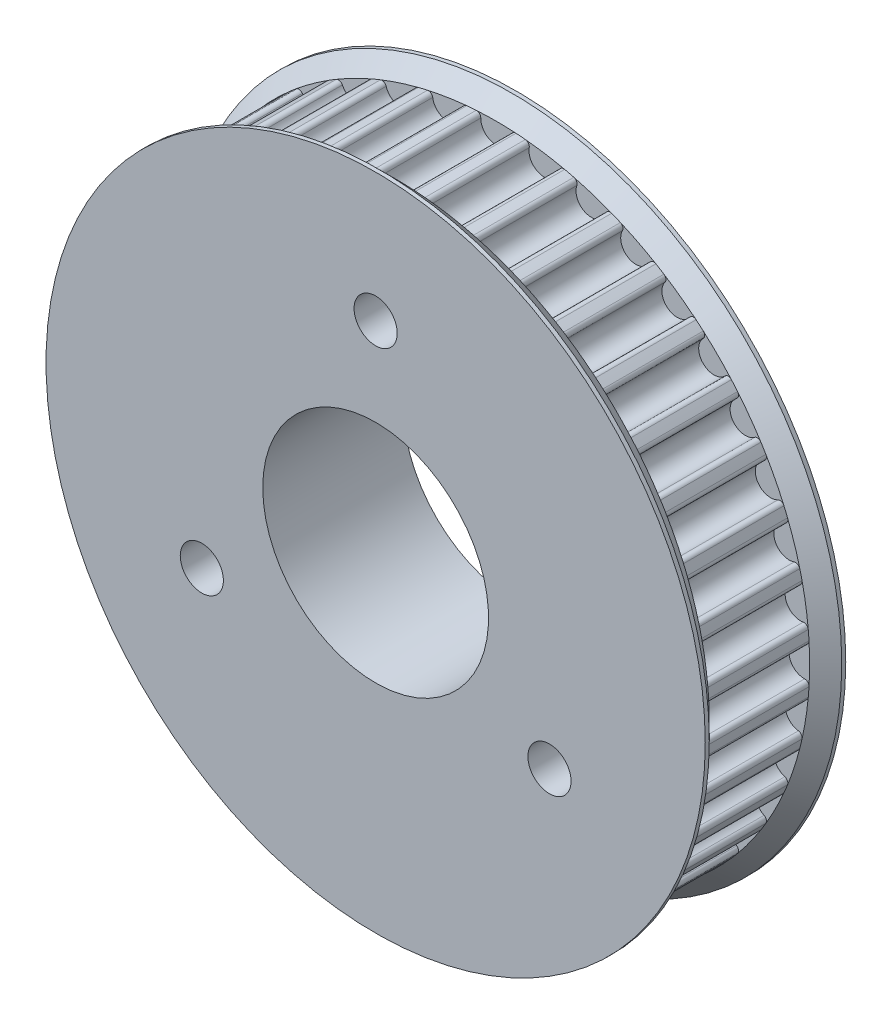
SolidWorks part; units mm, degrees
other "Markup1"
sketch "Sketch10" plane through (-16.9255, -16.9255, 12) normal (-0.253, -0.2476, 0.9352) x (0.4078, 0.8493, 0.3352)
ref_plane "Front Plane" through (0, 0, 0) normal (0, 0, 1) x (1, 0, 0)
ref_plane "Top Plane" through (0, 0, 0) normal (0, 1, 0) x (1, 0, 0)
ref_plane "Right Plane" through (0, 0, 0) normal (1, 0, 0) x (0, 0, -1)
sketch "Sketch1" plane through (0, 0, 0) normal (0, 0, 1) x (1, 0, 0)
  line L0 (0, 31.831) -> (0, 0) construction
  line L1 (0, 0) -> (4.9795, 31.4391) construction
  line L2 (0, 30.706) -> (1.9545, 30.7489) construction
  line L3 (2.8797, 30.6761) -> (4.8035, 30.3279) construction
  line L4 (1.9545, 30.7489) -> (1.9818, 31.1781) construction
  line L5 (2.8797, 30.6761) -> (2.9199, 31.1042) construction
  arc A0 (0, 31.831) -> (4.9795, 31.4391) centre (0, 0) cw construction
  circle A1 centre (0, 0) radius 31.831 construction
  circle A2 centre (0, 0) radius 31.241
  circle A3 centre (0, 0) radius 29.181
  circle A8 centre (0, 0) radius 32.981 construction
  circle A9 centre (0, 30.706) radius 1.525
  circle A10 centre (4.8035, 30.3279) radius 1.525
  circle A11 centre (1.9545, 30.7489) radius 0.43
  circle A12 centre (2.8797, 30.6761) radius 0.43
  point P18 (0, 29.181)
  point P19 (4.2572, 15.8881)
  point P20 (4.2572, 15.8881)
  point P21 (1.5246, 30.7395)
  point P23 (3.3029, 30.5995)
  dimension "D6" = 3.05
  dimension "D7" = 3.05
  dimension "D8" = 0.86
  dimension "D9" = 0.86
  dimension "D5" = 3.8
  dimension "D1" = 9
  dimension "D2" = 5
  dimension "D3" = 0.59
  dimension "D4" = 2.06
extrude "Boss-Extrude1" add sketch "Sketch1" along normal blind 10 contours A2
extrude "Cut-Extrude1" cut sketch "Sketch1<5>" along normal through all contours A11 A2 A9 | A12 A10 A2 | A9 | A10 region at (3.2858, 30.9603, 0) region at (1.5979, 31.0932, 0)
sketch "Sketch1<5>" plane through (0, 0, 0) normal (0, 0, 1) x (1, 0, 0) same geometry as "Sketch1"
pattern_circular "CirPattern3" count 40 over 360 about axis through (0, 0, 10) along (0, 0, 1) of "Cut-Extrude1"
sketch "Sketch2" plane through (0, 0, 10) normal (0, 0, 1) x (1, 0, 0)
  circle A0 centre (0, 0) radius 32.981 construction
  arc A81 (-30.7395, -1.5246) -> (-30.7395, 1.5246) centre (-30.706, 0) ccw
  arc A82 (-30.7395, -1.5246) -> (-30.7395, 1.5246) centre (-30.706, 0) ccw
  arc A83 (-30.7395, -1.5246) -> (-31.1781, -1.9818) centre (-30.7489, -1.9545) ccw
  arc A84 (-30.7395, -1.5246) -> (-31.1781, -1.9818) centre (-30.7489, -1.9545) ccw
  arc A85 (-31.1781, -1.9818) -> (-31.1042, -2.9199) centre (0, 0) ccw
  arc A86 (-31.1781, -1.9818) -> (-31.1042, -2.9199) centre (0, 0) ccw
  arc A87 (-31.1042, -2.9199) -> (-30.5995, -3.3029) centre (-30.6761, -2.8797) ccw
  arc A88 (-31.1042, -2.9199) -> (-30.5995, -3.3029) centre (-30.6761, -2.8797) ccw
  arc A89 (-30.1225, -6.3146) -> (-30.5995, -3.3029) centre (-30.3279, -4.8035) ccw
  arc A90 (-30.1225, -6.3146) -> (-30.5995, -3.3029) centre (-30.3279, -4.8035) ccw
  arc A91 (-30.1225, -6.3146) -> (-30.4842, -6.8347) centre (-30.0646, -6.7407) ccw
  arc A92 (-30.1225, -6.3146) -> (-30.4842, -6.8347) centre (-30.0646, -6.7407) ccw
  arc A93 (-30.4842, -6.8347) -> (-30.2645, -7.7497) centre (0, 0) ccw
  arc A95 (-30.4842, -6.8347) -> (-30.2645, -7.7497) centre (0, 0) ccw
  arc A97 (-30.2645, -7.7497) -> (-29.7061, -8.049) centre (-29.848, -7.6431) ccw
  arc A99 (-30.2645, -7.7497) -> (-29.7061, -8.049) centre (-29.848, -7.6431) ccw
  arc A101 (-28.7639, -10.949) -> (-29.7061, -8.049) centre (-29.2031, -9.4887) ccw
  arc A103 (-28.7639, -10.949) -> (-29.7061, -8.049) centre (-29.2031, -9.4887) ccw
  arc A105 (-28.7639, -10.949) -> (-29.0397, -11.5194) centre (-28.64, -11.3608) ccw
  arc A107 (-28.7639, -10.949) -> (-29.0397, -11.5194) centre (-28.64, -11.3608) ccw
  arc A109 (-29.0397, -11.5194) -> (-28.6796, -12.3887) centre (0, 0) ccw
  arc A111 (-29.0397, -11.5194) -> (-28.6796, -12.3887) centre (0, 0) ccw
  arc A112 (-28.6796, -12.3887) -> (-28.0813, -12.597) centre (-28.2848, -12.2182) ccw
  arc A114 (-28.6796, -12.3887) -> (-28.0813, -12.597) centre (-28.2848, -12.2182) ccw
  arc A116 (-26.6969, -15.3139) -> (-28.0813, -12.597) centre (-27.3592, -13.9402) ccw
  arc A118 (-26.6969, -15.3139) -> (-28.0813, -12.597) centre (-27.3592, -13.9402) ccw
  arc A122 (-26.6969, -15.3139) -> (-26.8801, -15.9203) centre (-26.5102, -15.7012) ccw
  arc A126 (-26.6969, -15.3139) -> (-26.8801, -15.9203) centre (-26.5102, -15.7012) ccw
  arc A130 (-26.8801, -15.9203) -> (-26.3885, -16.7227) centre (0, 0) ccw
  arc A134 (-26.8801, -15.9203) -> (-26.3885, -16.7227) centre (0, 0) ccw
  arc A138 (-26.3885, -16.7227) -> (-25.7649, -16.8348) centre (-26.0253, -16.4925) ccw
  arc A142 (-26.3885, -16.7227) -> (-25.7649, -16.8348) centre (-26.0253, -16.4925) ccw
  arc A146 (-23.9726, -19.3017) -> (-25.7649, -16.8348) centre (-24.8417, -18.0485) ccw
  arc A150 (-23.9726, -19.3017) -> (-25.7649, -16.8348) centre (-24.8417, -18.0485) ccw
  arc A154 (-23.9726, -19.3017) -> (-24.0587, -19.9293) centre (-23.7276, -19.655) ccw
  arc A158 (-23.9726, -19.3017) -> (-24.0587, -19.9293) centre (-23.7276, -19.655) ccw
  arc A162 (-24.0587, -19.9293) -> (-23.4476, -20.6449) centre (0, 0) ccw
  arc A166 (-24.0587, -19.9293) -> (-23.4476, -20.6449) centre (0, 0) ccw
  arc A170 (-23.4476, -20.6449) -> (-22.8142, -20.658) centre (-23.1248, -20.3607) ccw
  arc A174 (-23.4476, -20.6449) -> (-22.8142, -20.658) centre (-23.1248, -20.3607) ccw
  arc A178 (-20.658, -22.8142) -> (-22.8142, -20.658) centre (-21.7124, -21.7124) ccw
  arc A182 (-20.658, -22.8142) -> (-22.8142, -20.658) centre (-21.7124, -21.7124) ccw
  arc A186 (-20.658, -22.8142) -> (-20.6449, -23.4476) centre (-20.3607, -23.1248) ccw
  arc A190 (-20.658, -22.8142) -> (-20.6449, -23.4476) centre (-20.3607, -23.1248) ccw
  arc A193 (-20.6449, -23.4476) -> (-19.9293, -24.0587) centre (0, 0) ccw
  arc A195 (-20.6449, -23.4476) -> (-19.9293, -24.0587) centre (0, 0) ccw
  arc A197 (-19.9293, -24.0587) -> (-19.3017, -23.9726) centre (-19.655, -23.7276) ccw
  arc A199 (-19.9293, -24.0587) -> (-19.3017, -23.9726) centre (-19.655, -23.7276) ccw
  arc A201 (-16.8348, -25.7649) -> (-19.3017, -23.9726) centre (-18.0485, -24.8417) ccw
  arc A203 (-16.8348, -25.7649) -> (-19.3017, -23.9726) centre (-18.0485, -24.8417) ccw
  arc A205 (-16.8348, -25.7649) -> (-16.7227, -26.3885) centre (-16.4925, -26.0253) ccw
  arc A207 (-16.8348, -25.7649) -> (-16.7227, -26.3885) centre (-16.4925, -26.0253) ccw
  arc A209 (-16.7227, -26.3885) -> (-15.9203, -26.8801) centre (0, 0) ccw
  arc A211 (-16.7227, -26.3885) -> (-15.9203, -26.8801) centre (0, 0) ccw
  arc A213 (-15.9203, -26.8801) -> (-15.3139, -26.6969) centre (-15.7012, -26.5102) ccw
  arc A215 (-15.9203, -26.8801) -> (-15.3139, -26.6969) centre (-15.7012, -26.5102) ccw
  arc A217 (-12.597, -28.0813) -> (-15.3139, -26.6969) centre (-13.9402, -27.3592) ccw
  arc A221 (-12.597, -28.0813) -> (-15.3139, -26.6969) centre (-13.9402, -27.3592) ccw
  arc A225 (-12.597, -28.0813) -> (-12.3887, -28.6796) centre (-12.2182, -28.2848) ccw
  arc A229 (-12.597, -28.0813) -> (-12.3887, -28.6796) centre (-12.2182, -28.2848) ccw
  arc A233 (-12.3887, -28.6796) -> (-11.5194, -29.0397) centre (0, 0) ccw
  arc A241 (-12.3887, -28.6796) -> (-11.5194, -29.0397) centre (0, 0) ccw
  arc A245 (-11.5194, -29.0397) -> (-10.949, -28.7639) centre (-11.3608, -28.64) ccw
  arc A247 (-11.5194, -29.0397) -> (-10.949, -28.7639) centre (-11.3608, -28.64) ccw
  arc A249 (-8.049, -29.7061) -> (-10.949, -28.7639) centre (-9.4887, -29.2031) ccw
  arc A251 (-8.049, -29.7061) -> (-10.949, -28.7639) centre (-9.4887, -29.2031) ccw
  arc A253 (-8.049, -29.7061) -> (-7.7497, -30.2645) centre (-7.6431, -29.848) ccw
  arc A255 (-8.049, -29.7061) -> (-7.7497, -30.2645) centre (-7.6431, -29.848) ccw
  arc A257 (-7.7497, -30.2645) -> (-6.8347, -30.4842) centre (0, 0) ccw
  arc A259 (-7.7497, -30.2645) -> (-6.8347, -30.4842) centre (0, 0) ccw
  arc A261 (-6.8347, -30.4842) -> (-6.3146, -30.1225) centre (-6.7407, -30.0646) ccw
  arc A263 (-6.8347, -30.4842) -> (-6.3146, -30.1225) centre (-6.7407, -30.0646) ccw
  arc A373 (3.3029, 30.5995) -> (6.3146, 30.1225) centre (4.8035, 30.3279) ccw
  arc A374 (3.3029, 30.5995) -> (2.9199, 31.1042) centre (2.8797, 30.6761) ccw
  arc A375 (2.9199, 31.1042) -> (1.9818, 31.1781) centre (0, 0) ccw
  arc A376 (1.9818, 31.1781) -> (1.5246, 30.7395) centre (1.9545, 30.7489) ccw
  arc A377 (-1.5246, 30.7395) -> (1.5246, 30.7395) centre (0, 30.706) ccw
  arc A378 (-1.5246, 30.7395) -> (-1.9818, 31.1781) centre (-1.9545, 30.7489) ccw
  arc A379 (-1.9818, 31.1781) -> (-2.9199, 31.1042) centre (0, 0) ccw
  arc A380 (-2.9199, 31.1042) -> (-3.3029, 30.5995) centre (-2.8797, 30.6761) ccw
  arc A381 (-6.3146, 30.1225) -> (-3.3029, 30.5995) centre (-4.8035, 30.3279) ccw
  arc A382 (-6.3146, 30.1225) -> (-6.8347, 30.4842) centre (-6.7407, 30.0646) ccw
  arc A383 (-6.8347, 30.4842) -> (-7.7497, 30.2645) centre (0, 0) ccw
  arc A384 (-7.7497, 30.2645) -> (-8.049, 29.7061) centre (-7.6431, 29.848) ccw
  arc A385 (-10.949, 28.7639) -> (-8.049, 29.7061) centre (-9.4887, 29.2031) ccw
  arc A386 (-10.949, 28.7639) -> (-11.5194, 29.0397) centre (-11.3608, 28.64) ccw
  arc A387 (-11.5194, 29.0397) -> (-12.3887, 28.6796) centre (0, 0) ccw
  arc A388 (-12.3887, 28.6796) -> (-12.597, 28.0813) centre (-12.2182, 28.2848) ccw
  arc A389 (-15.3139, 26.6969) -> (-12.597, 28.0813) centre (-13.9402, 27.3592) ccw
  arc A390 (-15.3139, 26.6969) -> (-15.9203, 26.8801) centre (-15.7012, 26.5102) ccw
  arc A391 (-15.9203, 26.8801) -> (-16.7227, 26.3885) centre (0, 0) ccw
  arc A392 (-16.7227, 26.3885) -> (-16.8348, 25.7649) centre (-16.4925, 26.0253) ccw
  arc A393 (-19.3017, 23.9726) -> (-16.8348, 25.7649) centre (-18.0485, 24.8417) ccw
  arc A394 (-19.3017, 23.9726) -> (-19.9293, 24.0587) centre (-19.655, 23.7276) ccw
  arc A395 (-19.9293, 24.0587) -> (-20.6449, 23.4476) centre (0, 0) ccw
  arc A396 (-20.6449, 23.4476) -> (-20.658, 22.8142) centre (-20.3607, 23.1248) ccw
  arc A397 (-22.8142, 20.658) -> (-20.658, 22.8142) centre (-21.7124, 21.7124) ccw
  arc A398 (-22.8142, 20.658) -> (-23.4476, 20.6449) centre (-23.1248, 20.3607) ccw
  arc A399 (-23.4476, 20.6449) -> (-24.0587, 19.9293) centre (0, 0) ccw
  arc A400 (-24.0587, 19.9293) -> (-23.9726, 19.3017) centre (-23.7276, 19.655) ccw
  arc A401 (-25.7649, 16.8348) -> (-23.9726, 19.3017) centre (-24.8417, 18.0485) ccw
  arc A402 (-25.7649, 16.8348) -> (-26.3885, 16.7227) centre (-26.0253, 16.4925) ccw
  arc A403 (-26.3885, 16.7227) -> (-26.8801, 15.9203) centre (0, 0) ccw
  arc A404 (-26.8801, 15.9203) -> (-26.6969, 15.3139) centre (-26.5102, 15.7012) ccw
  arc A405 (-28.0813, 12.597) -> (-26.6969, 15.3139) centre (-27.3592, 13.9402) ccw
  arc A406 (-28.0813, 12.597) -> (-28.6796, 12.3887) centre (-28.2848, 12.2182) ccw
  arc A407 (-28.6796, 12.3887) -> (-29.0397, 11.5194) centre (0, 0) ccw
  arc A408 (-29.0397, 11.5194) -> (-28.7639, 10.949) centre (-28.64, 11.3608) ccw
  arc A409 (-29.7061, 8.049) -> (-28.7639, 10.949) centre (-29.2031, 9.4887) ccw
  arc A410 (-29.7061, 8.049) -> (-30.2645, 7.7497) centre (-29.848, 7.6431) ccw
  arc A411 (-30.2645, 7.7497) -> (-30.4842, 6.8347) centre (0, 0) ccw
  arc A412 (-30.4842, 6.8347) -> (-30.1225, 6.3146) centre (-30.0646, 6.7407) ccw
  arc A413 (-30.5995, 3.3029) -> (-30.1225, 6.3146) centre (-30.3279, 4.8035) ccw
  arc A414 (-30.5995, 3.3029) -> (-31.1042, 2.9199) centre (-30.6761, 2.8797) ccw
  arc A415 (-31.1042, 2.9199) -> (-31.1781, 1.9818) centre (0, 0) ccw
  arc A416 (-31.1781, 1.9818) -> (-30.7395, 1.5246) centre (-30.7489, 1.9545) ccw
  arc A649 (3.3029, 30.5995) -> (6.3146, 30.1225) centre (4.8035, 30.3279) ccw
  arc A650 (3.3029, 30.5995) -> (2.9199, 31.1042) centre (2.8797, 30.6761) ccw
  arc A651 (2.9199, 31.1042) -> (1.9818, 31.1781) centre (0, 0) ccw
  arc A652 (1.9818, 31.1781) -> (1.5246, 30.7395) centre (1.9545, 30.7489) ccw
  arc A653 (-1.5246, 30.7395) -> (1.5246, 30.7395) centre (0, 30.706) ccw
  arc A654 (-1.5246, 30.7395) -> (-1.9818, 31.1781) centre (-1.9545, 30.7489) ccw
  arc A655 (-1.9818, 31.1781) -> (-2.9199, 31.1042) centre (0, 0) ccw
  arc A656 (-2.9199, 31.1042) -> (-3.3029, 30.5995) centre (-2.8797, 30.6761) ccw
  arc A657 (-6.3146, 30.1225) -> (-3.3029, 30.5995) centre (-4.8035, 30.3279) ccw
  arc A658 (-6.3146, 30.1225) -> (-6.8347, 30.4842) centre (-6.7407, 30.0646) ccw
  arc A659 (-6.8347, 30.4842) -> (-7.7497, 30.2645) centre (0, 0) ccw
  arc A660 (-7.7497, 30.2645) -> (-8.049, 29.7061) centre (-7.6431, 29.848) ccw
  arc A661 (-10.949, 28.7639) -> (-8.049, 29.7061) centre (-9.4887, 29.2031) ccw
  arc A662 (-10.949, 28.7639) -> (-11.5194, 29.0397) centre (-11.3608, 28.64) ccw
  arc A663 (-11.5194, 29.0397) -> (-12.3887, 28.6796) centre (0, 0) ccw
  arc A664 (-12.3887, 28.6796) -> (-12.597, 28.0813) centre (-12.2182, 28.2848) ccw
  arc A665 (-15.3139, 26.6969) -> (-12.597, 28.0813) centre (-13.9402, 27.3592) ccw
  arc A666 (-15.3139, 26.6969) -> (-15.9203, 26.8801) centre (-15.7012, 26.5102) ccw
  arc A667 (-15.9203, 26.8801) -> (-16.7227, 26.3885) centre (0, 0) ccw
  arc A668 (-16.7227, 26.3885) -> (-16.8348, 25.7649) centre (-16.4925, 26.0253) ccw
  arc A669 (-19.3017, 23.9726) -> (-16.8348, 25.7649) centre (-18.0485, 24.8417) ccw
  arc A670 (-19.3017, 23.9726) -> (-19.9293, 24.0587) centre (-19.655, 23.7276) ccw
  arc A671 (-19.9293, 24.0587) -> (-20.6449, 23.4476) centre (0, 0) ccw
  arc A672 (-20.6449, 23.4476) -> (-20.658, 22.8142) centre (-20.3607, 23.1248) ccw
  arc A673 (-22.8142, 20.658) -> (-20.658, 22.8142) centre (-21.7124, 21.7124) ccw
  arc A674 (-22.8142, 20.658) -> (-23.4476, 20.6449) centre (-23.1248, 20.3607) ccw
  arc A675 (-23.4476, 20.6449) -> (-24.0587, 19.9293) centre (0, 0) ccw
  arc A676 (-24.0587, 19.9293) -> (-23.9726, 19.3017) centre (-23.7276, 19.655) ccw
  arc A677 (-25.7649, 16.8348) -> (-23.9726, 19.3017) centre (-24.8417, 18.0485) ccw
  arc A678 (-25.7649, 16.8348) -> (-26.3885, 16.7227) centre (-26.0253, 16.4925) ccw
  arc A679 (-26.3885, 16.7227) -> (-26.8801, 15.9203) centre (0, 0) ccw
  arc A680 (-26.8801, 15.9203) -> (-26.6969, 15.3139) centre (-26.5102, 15.7012) ccw
  arc A681 (-28.0813, 12.597) -> (-26.6969, 15.3139) centre (-27.3592, 13.9402) ccw
  arc A682 (-28.0813, 12.597) -> (-28.6796, 12.3887) centre (-28.2848, 12.2182) ccw
  arc A683 (-28.6796, 12.3887) -> (-29.0397, 11.5194) centre (0, 0) ccw
  arc A684 (-29.0397, 11.5194) -> (-28.7639, 10.949) centre (-28.64, 11.3608) ccw
  arc A685 (-29.7061, 8.049) -> (-28.7639, 10.949) centre (-29.2031, 9.4887) ccw
  arc A686 (-29.7061, 8.049) -> (-30.2645, 7.7497) centre (-29.848, 7.6431) ccw
  arc A687 (-30.2645, 7.7497) -> (-30.4842, 6.8347) centre (0, 0) ccw
  arc A688 (-30.4842, 6.8347) -> (-30.1225, 6.3146) centre (-30.0646, 6.7407) ccw
  arc A689 (-30.5995, 3.3029) -> (-30.1225, 6.3146) centre (-30.3279, 4.8035) ccw
  arc A690 (-30.5995, 3.3029) -> (-31.1042, 2.9199) centre (-30.6761, 2.8797) ccw
  arc A691 (-31.1042, 2.9199) -> (-31.1781, 1.9818) centre (0, 0) ccw
  arc A692 (-31.1781, 1.9818) -> (-30.7395, 1.5246) centre (-30.7489, 1.9545) ccw
  arc A715 (-3.3029, -30.5995) -> (-6.3146, -30.1225) centre (-4.8035, -30.3279) ccw
  arc A716 (-3.3029, -30.5995) -> (-6.3146, -30.1225) centre (-4.8035, -30.3279) ccw
  arc A717 (-3.3029, -30.5995) -> (-2.9199, -31.1042) centre (-2.8797, -30.6761) ccw
  arc A718 (-3.3029, -30.5995) -> (-2.9199, -31.1042) centre (-2.8797, -30.6761) ccw
  arc A719 (-2.9199, -31.1042) -> (-1.9818, -31.1781) centre (0, 0) ccw
  arc A720 (-2.9199, -31.1042) -> (-1.9818, -31.1781) centre (0, 0) ccw
  arc A721 (-1.9818, -31.1781) -> (-1.5246, -30.7395) centre (-1.9545, -30.7489) ccw
  arc A722 (-1.9818, -31.1781) -> (-1.5246, -30.7395) centre (-1.9545, -30.7489) ccw
  arc A723 (1.5246, -30.7395) -> (-1.5246, -30.7395) centre (0, -30.706) ccw
  arc A724 (1.5246, -30.7395) -> (-1.5246, -30.7395) centre (0, -30.706) ccw
  arc A725 (1.5246, -30.7395) -> (1.9818, -31.1781) centre (1.9545, -30.7489) ccw
  arc A726 (1.5246, -30.7395) -> (1.9818, -31.1781) centre (1.9545, -30.7489) ccw
  arc A727 (1.9818, -31.1781) -> (2.9199, -31.1042) centre (0, 0) ccw
  arc A728 (1.9818, -31.1781) -> (2.9199, -31.1042) centre (0, 0) ccw
  arc A729 (2.9199, -31.1042) -> (3.3029, -30.5995) centre (2.8797, -30.6761) ccw
  arc A730 (2.9199, -31.1042) -> (3.3029, -30.5995) centre (2.8797, -30.6761) ccw
  arc A731 (6.3146, -30.1225) -> (3.3029, -30.5995) centre (4.8035, -30.3279) ccw
  arc A732 (6.3146, -30.1225) -> (3.3029, -30.5995) centre (4.8035, -30.3279) ccw
  arc A733 (6.3146, -30.1225) -> (6.8347, -30.4842) centre (6.7407, -30.0646) ccw
  arc A734 (6.3146, -30.1225) -> (6.8347, -30.4842) centre (6.7407, -30.0646) ccw
  arc A735 (6.8347, -30.4842) -> (7.7497, -30.2645) centre (0, 0) ccw
  arc A736 (6.8347, -30.4842) -> (7.7497, -30.2645) centre (0, 0) ccw
  arc A737 (7.7497, -30.2645) -> (8.049, -29.7061) centre (7.6431, -29.848) ccw
  arc A738 (7.7497, -30.2645) -> (8.049, -29.7061) centre (7.6431, -29.848) ccw
  arc A739 (10.949, -28.7639) -> (8.049, -29.7061) centre (9.4887, -29.2031) ccw
  arc A740 (10.949, -28.7639) -> (8.049, -29.7061) centre (9.4887, -29.2031) ccw
  arc A741 (10.949, -28.7639) -> (11.5194, -29.0397) centre (11.3608, -28.64) ccw
  arc A742 (10.949, -28.7639) -> (11.5194, -29.0397) centre (11.3608, -28.64) ccw
  arc A743 (11.5194, -29.0397) -> (12.3887, -28.6796) centre (0, 0) ccw
  arc A744 (11.5194, -29.0397) -> (12.3887, -28.6796) centre (0, 0) ccw
  arc A745 (12.3887, -28.6796) -> (12.597, -28.0813) centre (12.2182, -28.2848) ccw
  arc A746 (12.3887, -28.6796) -> (12.597, -28.0813) centre (12.2182, -28.2848) ccw
  arc A747 (15.3139, -26.6969) -> (12.597, -28.0813) centre (13.9402, -27.3592) ccw
  arc A748 (15.3139, -26.6969) -> (12.597, -28.0813) centre (13.9402, -27.3592) ccw
  arc A749 (15.3139, -26.6969) -> (15.9203, -26.8801) centre (15.7012, -26.5102) ccw
  arc A750 (15.3139, -26.6969) -> (15.9203, -26.8801) centre (15.7012, -26.5102) ccw
  arc A751 (15.9203, -26.8801) -> (16.7227, -26.3885) centre (0, 0) ccw
  arc A752 (15.9203, -26.8801) -> (16.7227, -26.3885) centre (0, 0) ccw
  arc A753 (16.7227, -26.3885) -> (16.8348, -25.7649) centre (16.4925, -26.0253) ccw
  arc A754 (16.7227, -26.3885) -> (16.8348, -25.7649) centre (16.4925, -26.0253) ccw
  arc A755 (19.3017, -23.9726) -> (16.8348, -25.7649) centre (18.0485, -24.8417) ccw
  arc A756 (19.3017, -23.9726) -> (16.8348, -25.7649) centre (18.0485, -24.8417) ccw
  arc A757 (19.3017, -23.9726) -> (19.9293, -24.0587) centre (19.655, -23.7276) ccw
  arc A758 (19.3017, -23.9726) -> (19.9293, -24.0587) centre (19.655, -23.7276) ccw
  arc A759 (19.9293, -24.0587) -> (20.6449, -23.4476) centre (0, 0) ccw
  arc A760 (19.9293, -24.0587) -> (20.6449, -23.4476) centre (0, 0) ccw
  arc A761 (20.6449, -23.4476) -> (20.658, -22.8142) centre (20.3607, -23.1248) ccw
  arc A762 (20.6449, -23.4476) -> (20.658, -22.8142) centre (20.3607, -23.1248) ccw
  arc A763 (22.8142, -20.658) -> (20.658, -22.8142) centre (21.7124, -21.7124) ccw
  arc A764 (22.8142, -20.658) -> (20.658, -22.8142) centre (21.7124, -21.7124) ccw
  arc A765 (22.8142, -20.658) -> (23.4476, -20.6449) centre (23.1248, -20.3607) ccw
  arc A766 (22.8142, -20.658) -> (23.4476, -20.6449) centre (23.1248, -20.3607) ccw
  arc A767 (23.4476, -20.6449) -> (24.0587, -19.9293) centre (0, 0) ccw
  arc A768 (23.4476, -20.6449) -> (24.0587, -19.9293) centre (0, 0) ccw
  arc A769 (24.0587, -19.9293) -> (23.9726, -19.3017) centre (23.7276, -19.655) ccw
  arc A770 (24.0587, -19.9293) -> (23.9726, -19.3017) centre (23.7276, -19.655) ccw
  arc A771 (25.7649, -16.8348) -> (23.9726, -19.3017) centre (24.8417, -18.0485) ccw
  arc A772 (25.7649, -16.8348) -> (23.9726, -19.3017) centre (24.8417, -18.0485) ccw
  arc A773 (25.7649, -16.8348) -> (26.3885, -16.7227) centre (26.0253, -16.4925) ccw
  arc A774 (25.7649, -16.8348) -> (26.3885, -16.7227) centre (26.0253, -16.4925) ccw
  arc A775 (26.3885, -16.7227) -> (26.8801, -15.9203) centre (0, 0) ccw
  arc A776 (26.3885, -16.7227) -> (26.8801, -15.9203) centre (0, 0) ccw
  arc A777 (26.8801, -15.9203) -> (26.6969, -15.3139) centre (26.5102, -15.7012) ccw
  arc A778 (26.8801, -15.9203) -> (26.6969, -15.3139) centre (26.5102, -15.7012) ccw
  arc A779 (28.0813, -12.597) -> (26.6969, -15.3139) centre (27.3592, -13.9402) ccw
  arc A780 (28.0813, -12.597) -> (26.6969, -15.3139) centre (27.3592, -13.9402) ccw
  arc A781 (28.0813, -12.597) -> (28.6796, -12.3887) centre (28.2848, -12.2182) ccw
  arc A782 (28.0813, -12.597) -> (28.6796, -12.3887) centre (28.2848, -12.2182) ccw
  arc A783 (28.6796, -12.3887) -> (29.0397, -11.5194) centre (0, 0) ccw
  arc A784 (28.6796, -12.3887) -> (29.0397, -11.5194) centre (0, 0) ccw
  arc A785 (29.0397, -11.5194) -> (28.7639, -10.949) centre (28.64, -11.3608) ccw
  arc A786 (29.0397, -11.5194) -> (28.7639, -10.949) centre (28.64, -11.3608) ccw
  arc A787 (29.7061, -8.049) -> (28.7639, -10.949) centre (29.2031, -9.4887) ccw
  arc A788 (29.7061, -8.049) -> (28.7639, -10.949) centre (29.2031, -9.4887) ccw
  arc A789 (29.7061, -8.049) -> (30.2645, -7.7497) centre (29.848, -7.6431) ccw
  arc A790 (29.7061, -8.049) -> (30.2645, -7.7497) centre (29.848, -7.6431) ccw
  arc A791 (30.2645, -7.7497) -> (30.4842, -6.8347) centre (0, 0) ccw
  arc A792 (30.2645, -7.7497) -> (30.4842, -6.8347) centre (0, 0) ccw
  arc A793 (30.4842, -6.8347) -> (30.1225, -6.3146) centre (30.0646, -6.7407) ccw
  arc A794 (30.4842, -6.8347) -> (30.1225, -6.3146) centre (30.0646, -6.7407) ccw
  arc A795 (30.5995, -3.3029) -> (30.1225, -6.3146) centre (30.3279, -4.8035) ccw
  arc A796 (30.5995, -3.3029) -> (30.1225, -6.3146) centre (30.3279, -4.8035) ccw
  arc A797 (30.5995, -3.3029) -> (31.1042, -2.9199) centre (30.6761, -2.8797) ccw
  arc A798 (30.5995, -3.3029) -> (31.1042, -2.9199) centre (30.6761, -2.8797) ccw
  arc A799 (31.1042, -2.9199) -> (31.1781, -1.9818) centre (0, 0) ccw
  arc A800 (31.1042, -2.9199) -> (31.1781, -1.9818) centre (0, 0) ccw
  arc A801 (31.1781, -1.9818) -> (30.7395, -1.5246) centre (30.7489, -1.9545) ccw
  arc A802 (31.1781, -1.9818) -> (30.7395, -1.5246) centre (30.7489, -1.9545) ccw
  arc A803 (30.7395, 1.5246) -> (30.7395, -1.5246) centre (30.706, 0) ccw
  arc A804 (30.7395, 1.5246) -> (30.7395, -1.5246) centre (30.706, 0) ccw
  arc A805 (30.7395, 1.5246) -> (31.1781, 1.9818) centre (30.7489, 1.9545) ccw
  arc A806 (30.7395, 1.5246) -> (31.1781, 1.9818) centre (30.7489, 1.9545) ccw
  arc A807 (31.1781, 1.9818) -> (31.1042, 2.9199) centre (0, 0) ccw
  arc A808 (31.1781, 1.9818) -> (31.1042, 2.9199) centre (0, 0) ccw
  arc A809 (31.1042, 2.9199) -> (30.5995, 3.3029) centre (30.6761, 2.8797) ccw
  arc A810 (31.1042, 2.9199) -> (30.5995, 3.3029) centre (30.6761, 2.8797) ccw
  arc A811 (30.1225, 6.3146) -> (30.5995, 3.3029) centre (30.3279, 4.8035) ccw
  arc A812 (30.1225, 6.3146) -> (30.5995, 3.3029) centre (30.3279, 4.8035) ccw
  arc A813 (30.1225, 6.3146) -> (30.4842, 6.8347) centre (30.0646, 6.7407) ccw
  arc A814 (30.1225, 6.3146) -> (30.4842, 6.8347) centre (30.0646, 6.7407) ccw
  arc A815 (30.4842, 6.8347) -> (30.2645, 7.7497) centre (0, 0) ccw
  arc A816 (30.4842, 6.8347) -> (30.2645, 7.7497) centre (0, 0) ccw
  arc A817 (30.2645, 7.7497) -> (29.7061, 8.049) centre (29.848, 7.6431) ccw
  arc A818 (30.2645, 7.7497) -> (29.7061, 8.049) centre (29.848, 7.6431) ccw
  arc A819 (28.7639, 10.949) -> (29.7061, 8.049) centre (29.2031, 9.4887) ccw
  arc A820 (28.7639, 10.949) -> (29.7061, 8.049) centre (29.2031, 9.4887) ccw
  arc A821 (28.7639, 10.949) -> (29.0397, 11.5194) centre (28.64, 11.3608) ccw
  arc A822 (28.7639, 10.949) -> (29.0397, 11.5194) centre (28.64, 11.3608) ccw
  arc A823 (29.0397, 11.5194) -> (28.6796, 12.3887) centre (0, 0) ccw
  arc A824 (29.0397, 11.5194) -> (28.6796, 12.3887) centre (0, 0) ccw
  arc A825 (28.6796, 12.3887) -> (28.0813, 12.597) centre (28.2848, 12.2182) ccw
  arc A826 (28.6796, 12.3887) -> (28.0813, 12.597) centre (28.2848, 12.2182) ccw
  arc A827 (26.6969, 15.3139) -> (28.0813, 12.597) centre (27.3592, 13.9402) ccw
  arc A828 (26.6969, 15.3139) -> (28.0813, 12.597) centre (27.3592, 13.9402) ccw
  arc A829 (26.6969, 15.3139) -> (26.8801, 15.9203) centre (26.5102, 15.7012) ccw
  arc A830 (26.6969, 15.3139) -> (26.8801, 15.9203) centre (26.5102, 15.7012) ccw
  arc A831 (26.8801, 15.9203) -> (26.3885, 16.7227) centre (0, 0) ccw
  arc A832 (26.8801, 15.9203) -> (26.3885, 16.7227) centre (0, 0) ccw
  arc A833 (26.3885, 16.7227) -> (25.7649, 16.8348) centre (26.0253, 16.4925) ccw
  arc A834 (26.3885, 16.7227) -> (25.7649, 16.8348) centre (26.0253, 16.4925) ccw
  arc A835 (23.9726, 19.3017) -> (25.7649, 16.8348) centre (24.8417, 18.0485) ccw
  arc A836 (23.9726, 19.3017) -> (25.7649, 16.8348) centre (24.8417, 18.0485) ccw
  arc A837 (23.9726, 19.3017) -> (24.0587, 19.9293) centre (23.7276, 19.655) ccw
  arc A838 (23.9726, 19.3017) -> (24.0587, 19.9293) centre (23.7276, 19.655) ccw
  arc A839 (24.0587, 19.9293) -> (23.4476, 20.6449) centre (0, 0) ccw
  arc A840 (24.0587, 19.9293) -> (23.4476, 20.6449) centre (0, 0) ccw
  arc A841 (23.4476, 20.6449) -> (22.8142, 20.658) centre (23.1248, 20.3607) ccw
  arc A842 (23.4476, 20.6449) -> (22.8142, 20.658) centre (23.1248, 20.3607) ccw
  arc A843 (20.658, 22.8142) -> (22.8142, 20.658) centre (21.7124, 21.7124) ccw
  arc A844 (20.658, 22.8142) -> (22.8142, 20.658) centre (21.7124, 21.7124) ccw
  arc A845 (20.658, 22.8142) -> (20.6449, 23.4476) centre (20.3607, 23.1248) ccw
  arc A846 (20.658, 22.8142) -> (20.6449, 23.4476) centre (20.3607, 23.1248) ccw
  arc A847 (20.6449, 23.4476) -> (19.9293, 24.0587) centre (0, 0) ccw
  arc A848 (20.6449, 23.4476) -> (19.9293, 24.0587) centre (0, 0) ccw
  arc A849 (19.9293, 24.0587) -> (19.3017, 23.9726) centre (19.655, 23.7276) ccw
  arc A850 (19.9293, 24.0587) -> (19.3017, 23.9726) centre (19.655, 23.7276) ccw
  arc A851 (16.8348, 25.7649) -> (19.3017, 23.9726) centre (18.0485, 24.8417) ccw
  arc A852 (16.8348, 25.7649) -> (19.3017, 23.9726) centre (18.0485, 24.8417) ccw
  arc A853 (16.8348, 25.7649) -> (16.7227, 26.3885) centre (16.4925, 26.0253) ccw
  arc A854 (16.8348, 25.7649) -> (16.7227, 26.3885) centre (16.4925, 26.0253) ccw
  arc A855 (16.7227, 26.3885) -> (15.9203, 26.8801) centre (0, 0) ccw
  arc A856 (16.7227, 26.3885) -> (15.9203, 26.8801) centre (0, 0) ccw
  arc A857 (15.9203, 26.8801) -> (15.3139, 26.6969) centre (15.7012, 26.5102) ccw
  arc A858 (15.9203, 26.8801) -> (15.3139, 26.6969) centre (15.7012, 26.5102) ccw
  arc A859 (12.597, 28.0813) -> (15.3139, 26.6969) centre (13.9402, 27.3592) ccw
  arc A860 (12.597, 28.0813) -> (15.3139, 26.6969) centre (13.9402, 27.3592) ccw
  arc A861 (12.597, 28.0813) -> (12.3887, 28.6796) centre (12.2182, 28.2848) ccw
  arc A862 (12.597, 28.0813) -> (12.3887, 28.6796) centre (12.2182, 28.2848) ccw
  arc A863 (12.3887, 28.6796) -> (11.5194, 29.0397) centre (0, 0) ccw
  arc A864 (12.3887, 28.6796) -> (11.5194, 29.0397) centre (0, 0) ccw
  arc A865 (11.5194, 29.0397) -> (10.949, 28.7639) centre (11.3608, 28.64) ccw
  arc A866 (11.5194, 29.0397) -> (10.949, 28.7639) centre (11.3608, 28.64) ccw
  arc A867 (8.049, 29.7061) -> (10.949, 28.7639) centre (9.4887, 29.2031) ccw
  arc A868 (8.049, 29.7061) -> (10.949, 28.7639) centre (9.4887, 29.2031) ccw
  arc A869 (8.049, 29.7061) -> (7.7497, 30.2645) centre (7.6431, 29.848) ccw
  arc A870 (8.049, 29.7061) -> (7.7497, 30.2645) centre (7.6431, 29.848) ccw
  arc A871 (7.7497, 30.2645) -> (6.8347, 30.4842) centre (0, 0) ccw
  arc A872 (7.7497, 30.2645) -> (6.8347, 30.4842) centre (0, 0) ccw
  arc A873 (6.8347, 30.4842) -> (6.3146, 30.1225) centre (6.7407, 30.0646) ccw
  arc A874 (6.8347, 30.4842) -> (6.3146, 30.1225) centre (6.7407, 30.0646) ccw
  point P0 (0.0074, 23.4631)
  point P4 (0.0074, 23.4631)
  point P7 (0, 32.981)
  point P10 (0, 32.981)
  point P19 (0, 32.981)
  point P22 (0, 32.981)
  point P25 (0.7493, 32.9725)
  dimension "D1" = 0
sketch "Sketch3" plane through (0, 0, 0) normal (0, 0, -1) x (-1, 0, 0)
  line L1 (2.5434, -1.3654) -> (2.4542, 1.5199)
  line L2 (2.4542, 1.5199) -> (-0.0892, 2.8854)
  line L3 (-0.0892, 2.8854) -> (-2.5434, 1.3654)
  line L4 (-2.5434, 1.3654) -> (-2.4542, -1.5199)
  line L5 (-2.4542, -1.5199) -> (0.0892, -2.8854)
  line L6 (0.0892, -2.8854) -> (2.5434, -1.3654)
  circle A0 centre (0, 0) radius 2.5 construction
  point P0 (0, 0)
  dimension "D1" = 5
extrude "Cut-Extrude2" [suppressed] cut sketch "Sketch3" against normal through all both and the other way through all
sketch "Sketch5" plane through (0, 0, 0) normal (1, 0, 0) x (0, 0, -1)
  line L1 (0, 0) -> (1.6, 0)
  line L2 (0, 0) -> (0, 31.241)
  line L3 (0, 31.241) -> (1.6, 31.241)
  line L4 (1.6, 0) -> (1.6, 31.241)
  line L6 (0, 31.241) -> (1.6, 32.841)
  line L7 (1.6, 0) -> (2, 0)
  line L8 (1.6, 0) -> (1.6, 32.841)
  line L9 (1.6, 32.841) -> (2, 32.841)
  line L10 (2, 0) -> (2, 32.841)
  dimension "D1" = 31.241
  dimension "D3" = 2
  dimension "D4" = 45
  dimension "D2" = 0.4
revolve "Revolve1" add sketch "Sketch5" angle 360 about L7 region at (0, 15.6205, -0.8) region at (0, 16.4205, -1.8) region at (0, 31.7743, -1.0667)
ref_plane "Plane1" through (0, 0, 5) normal (0, 0, 1) x (1, 0, 0)
mirror "Mirror1" about plane through (0, 0, 5) normal (0, 0, 1) of "Revolve1"
sketch "Sketch7" plane through (0, 0, -2) normal (0, 0, -1) x (-1, 0, 0)
  circle A1 centre (0, 20) radius 2.15
  circle A3 centre (0, 0) radius 11.25
  circle A4 centre (17.3205, -10) radius 2.15
  circle A5 centre (-17.3205, -10) radius 2.15
  point P11 (0, 0)
  point P20 (0, 0)
  dimension "D1" = 22.5
  dimension "D2" = 4.3
  dimension "D3" = 20
  dimension "D4" = 3
extrude "Cut-Extrude4" cut sketch "Sketch7" against normal through all
chamfer "Chamfer1" distance 2.6 angle 45 3 edges at (-2.15, 20, -2) (-19.4705, -10, -2) (15.1705, -10, -2)
equation "\"n\"= 40"
equation "\"D1@Sketch1\"=360/\"n\""
equation "\"D1@CirPattern3\"=\"n\""
equation "\"Width\"= 10"
equation "\"D1@Boss-Extrude1\"=\"Width\""
equation "\"D1@Sketch5\"=(\"n\"*5/pi-0.59*2)/2"
